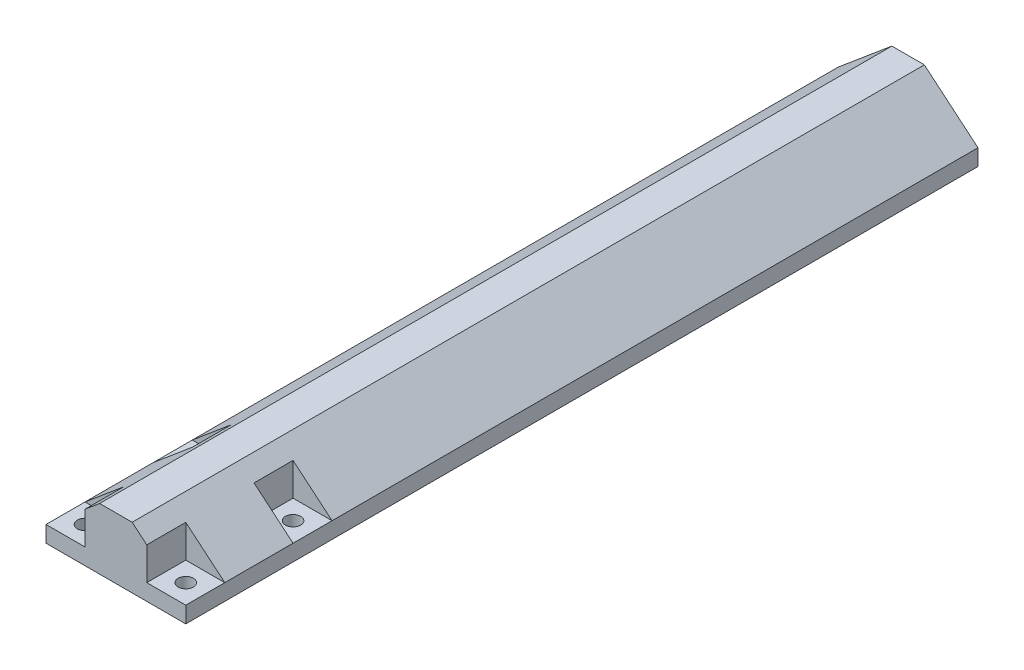
SolidWorks part; units mm, degrees
material "ABS"
ref_plane "Front Plane" through (0, 0, 0) normal (0, 0, 1) x (1, 0, 0)
ref_plane "Top Plane" through (0, 0, 0) normal (0, 1, 0) x (1, 0, 0)
ref_plane "Right Plane" through (0, 0, 0) normal (1, 0, 0) x (0, 0, -1)
sketch "Sketch1" plane through (0, 0, 0) normal (0, 1, 0) x (1, 0, 0)
  line L1 (-21.5, -22.5) -> (21.5, -22.5)
  line L2 (-21.5, -22.5) -> (-21.5, 22.5)
  line L3 (-21.5, 22.5) -> (21.5, 22.5)
  line L4 (21.5, -22.5) -> (21.5, 22.5)
  line L5 (-21.5, -22.5) -> (21.5, 22.5) construction
  line L6 (-21.5, 22.5) -> (21.5, -22.5) construction
  point P0 (0, 0)
  dimension "D1" = 45
  dimension "D2" = 43
extrude "Boss-Extrude1" add sketch "Sketch1" along normal blind 5
sketch "Sketch2" plane through (0, 5, 0) normal (0, 1, 0) x (1, 0, 0)
  line L0 (0, 22.5) -> (0, -22.5) construction
  line L1 (21.5, 22.5) -> (-21.5, 22.5) construction
  line L2 (-21.5, -22.5) -> (21.5, -22.5) construction
  line L3 (-21.5, 0) -> (21.5, 0) construction
  line L4 (-21.5, 22.5) -> (-21.5, -22.5) construction
  line L5 (21.5, -22.5) -> (21.5, 22.5) construction
  line L6 (-21.5, -16.5) -> (21.5, -16.5) construction
  line L7 (-15.5, 22.5) -> (-15.5, -22.5) construction
  circle A0 centre (-15.5, -16.5) radius 2.35
  circle A1 centre (-15.5, 16.5) radius 2.35
  circle A2 centre (15.5, 16.5) radius 2.35
  circle A3 centre (15.5, -16.5) radius 2.35
  point P19 (-15.5, -16.5)
  dimension "D3" = 4.7
  dimension "D1" = 6
  dimension "D2" = 6
sketch "Sketch3" plane through (0, 0, 0) normal (0, -1, 0) x (1, 0, 0)
  line L0 (0, -22.5) -> (0, 22.5) construction
  line L1 (0, -22.5) -> (0, 22.5)
sketch "Sketch4" plane through (0, 0, 0) normal (0, 0, 1) x (1, 0, 0)
  line L0 (-21.5, 5) -> (-5, 18.8451)
  line L1 (-5, 18.8451) -> (5, 18.8451)
  line L2 (5, 18.8451) -> (21.5, 5)
  line L3 (-21.5, 5) -> (21.5, 5) construction
  line L4 (21.5, 5) -> (-21.5, 5)
  line L5 (-21.5, 5) -> (-21.5, 0)
  line L6 (-21.5, 0) -> (21.5, 0)
  line L7 (21.5, 0) -> (21.5, 5)
  point P0 (-21.5, 5)
  point P2 (21.5, 5)
  dimension "D1" = 10
  dimension "D2" = 40
  dimension "D3" = 40
extrude "Boss-Extrude2" add sketch "Sketch4" along normal up to surface (22.5 mm away) and the other way blind 221.2232 contours L4 L2 L1 L0 | L6 L7 L4 L5 region at (0, 10.4858, 0) region at (0, 2.5, 0) up to face at (0, 2.5, 22.5)
sketch "Sketch5" plane through (0, 0, 0) normal (0, -1, 0) x (1, 0, 0)
  line L0 (21.5, 22.5) -> (21.5, -221.2232) construction
  line L1 (-21.5, -221.2232) -> (-21.5, 22.5) construction
  line L2 (5, 22.5) -> (5, -221.2232) construction
  line L3 (-5, 22.5) -> (-5, -221.2232) construction
  line L4 (21.5, 22.5) -> (21.5, -221.2232)
  line L5 (-21.5, -221.2232) -> (-21.5, 22.5)
  line L6 (5, 22.5) -> (5, -221.2232)
  line L7 (-5, 22.5) -> (-5, -221.2232)
  line L8 (-9.5, 22.5) -> (-9.5, -40)
  line L9 (-21.5, 22.5) -> (21.5, 22.5) construction
  circle A0 centre (15.5, -16.5) radius 2.35 construction
  circle A1 centre (-15.5, -16.5) radius 2.35 construction
  circle A2 centre (15.5, 16.5) radius 2.35 construction
  circle A3 centre (-15.5, 16.5) radius 2.35 construction
  circle A4 centre (15.5, -16.5) radius 2.35
  circle A5 centre (-15.5, -16.5) radius 2.35
  circle A6 centre (15.5, 16.5) radius 2.35
  circle A7 centre (-15.5, 16.5) radius 2.35
  point P24 (-9.5, -40)
  point P26 (-9.5, -22.5)
  point P27 (0, 0)
  dimension "D1" = 6
extrude "Cut-Extrude2" cut sketch "Sketch5" against normal through all contours A4 | A5 | A7 | A6 region at (15.5, 0, -16.5) region at (-15.5, 0, -16.5) region at (15.5, 0, 16.5) region at (-15.5, 0, 16.5)
sketch "Sketch6" plane through (0, 18.8451, 0) normal (0, 1, 0) x (1, 0, 0)
  line L0 (-21.5, 221.2232) -> (-21.5, -22.5) construction
  line L1 (-9.5, -22.5) -> (-9.5, 40) construction
  line L2 (-21.5, 221.2232) -> (-21.5, -22.5)
  line L3 (-9.5, -22.5) -> (-9.5, 40)
  line L5 (0, -10.3648) -> (0, 10.3648) construction
  line L6 (9.5, -22.5) -> (9.5, 221.2232)
  line L7 (21.5, 221.2232) -> (21.5, -22.5)
  line L8 (-21.5, 10.5) -> (21.5, 10.5)
  line L9 (-21.5, -10.5) -> (21.5, -10.5)
  line L11 (9.5, 221.2232) -> (21.5, 221.2232)
  line L12 (9.5, -22.5) -> (21.5, -22.5)
  line L13 (-9.5, -22.5) -> (-21.5, -22.5)
  line L14 (-21.5, 22.5) -> (21.5, 22.5)
  line L15 (-9.5, 40) -> (-21.5, 40)
  circle A0 centre (15.5, -16.5) radius 2.35 construction
  circle A1 centre (-15.5, -16.5) radius 2.35 construction
  circle A2 centre (15.5, 16.5) radius 2.35 construction
  circle A3 centre (-15.5, 16.5) radius 2.35 construction
  circle A4 centre (15.5, -16.5) radius 2.35 construction
  circle A5 centre (-15.5, -16.5) radius 2.35 construction
  circle A6 centre (15.5, 16.5) radius 2.35 construction
  circle A7 centre (-15.5, 16.5) radius 2.35 construction
  point P28 (9.5, 221.2232)
  dimension "D1" = 6
  dimension "D2" = 6
  dimension "D3" = 6
  dimension "D4" = 12
  dimension "D5" = 12
extrude "Cut-Extrude3" cut sketch "Sketch6" against normal up to vertex (13.8451 mm away) contours L6 L12 L7 L9 | L11 L6 L8 L7 | L2 L8 L3 | L13 L3 L9 L2 region at (-15.5, 18.8451, -16.5) region at (-15.5, 18.8451, 16.5) region at (15.5, 18.8451, -16.5) region at (15.5, 18.8451, 16.5) up to point (21.5, 5, 22.5)
